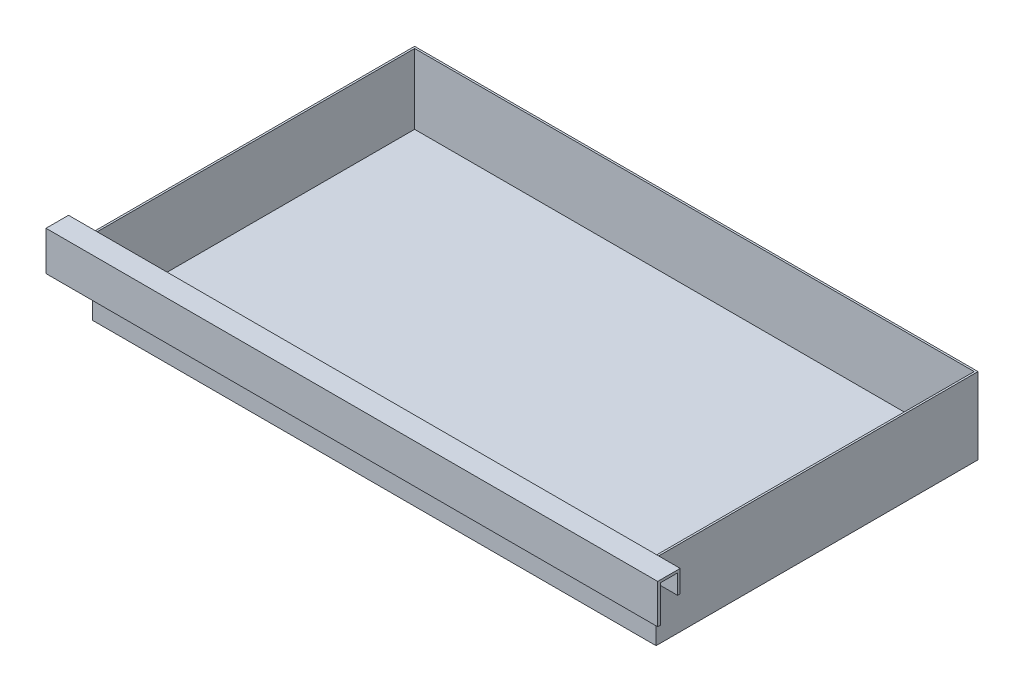
SolidWorks part; units mm, degrees
material "AISI 4130 Steel, normalized at 870C"
ref_plane "Front Plane" through (0, 0, 0) normal (0, 0, 1) x (1, 0, 0)
ref_plane "Top Plane" through (0, 0, 0) normal (0, 1, 0) x (1, 0, 0)
ref_plane "Right Plane" through (0, 0, 0) normal (1, 0, 0) x (0, 0, -1)
sketch "Sketch1" plane through (0, 0, 0) normal (0, 1, 0) x (1, 0, 0)
  line L0 (-111.125, 0) -> (111.125, 0)
  line L1 (111.125, 0) -> (111.125, 127)
  line L2 (111.125, 127) -> (-111.125, 127)
  line L3 (-111.125, 127) -> (-111.125, 0)
  line L4 (-110.3757, 126.2507) -> (-110.3757, 0.7493)
  line L5 (-110.3757, 0.7493) -> (110.3757, 0.7493)
  line L6 (110.3757, 0.7493) -> (110.3757, 126.2507)
  line L7 (110.3757, 126.2507) -> (-110.3757, 126.2507)
  point P9 (0, 0)
  dimension "D2" = 127
  dimension "D3" = 222.25
  dimension "D1" = 0.7493
extrude "Base" add sketch "Sketch1" along normal blind 2.54 contours L2 L3 L0 L1 | L6 L7 L4 L5 L3 L2 L1 L0 region at (-110.869, 0, -63.5) region at (0, 0, -63.5)
extrude "Walls" add sketch "Sketch1<3>" along normal blind 30.1625
sketch "Sketch1<3>" plane through (0, 0, 0) normal (0, 1, 0) x (1, 0, 0) same geometry as "Sketch1"
sketch "Sketch2" plane through (0, 0, 0) normal (1, 0, 0) x (0, 0, -1)
  line L2 (0, 22.4754) -> (0, 31.1785)
  line L3 (0, 31.1785) -> (-8.89, 31.1785)
  line L4 (-8.89, 31.1785) -> (-8.89, 15.6845)
  line L9 (-1.016, 22.4754) -> (-1.016, 30.1625)
  line L10 (-1.016, 30.1625) -> (-7.874, 30.1625)
  line L11 (-7.874, 30.1625) -> (-7.874, 15.6845)
  line L12 (-8.89, 15.6845) -> (-7.874, 15.6845)
  line L13 (-1.016, 22.4754) -> (0, 22.4754)
  line L15 (0, 30.1625) -> (127, 30.1625) construction
  dimension "D1" = 1.016
  dimension "D2" = 8.89
  dimension "D3" = 15.494
  dimension "D4" = 8.7031
extrude "Handle" add sketch "Sketch2" along normal blind 120.65 and the other way blind 120.65
